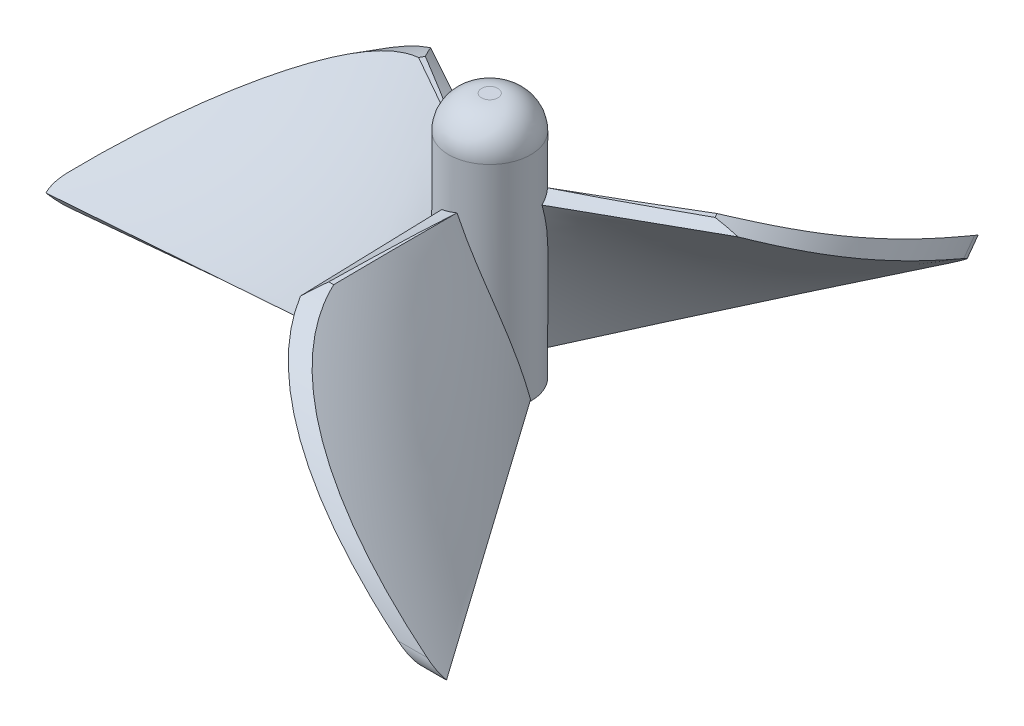
SolidWorks part; units mm, degrees
material "ABS"
ref_plane "Front Plane" through (0, 0, 0) normal (0, 0, 1) x (1, 0, 0)
ref_plane "Top Plane" through (0, 0, 0) normal (0, 1, 0) x (1, 0, 0)
ref_plane "Right Plane" through (0, 0, 0) normal (1, 0, 0) x (0, 0, -1)
sketch "Sketch1" plane through (0, 0, 0) normal (0, 1, 0) x (1, 0, 0)
  circle A0 centre (0, 0) radius 2.5
extrude "Boss-Extrude1" add sketch "Sketch1" along normal blind 15
sketch "Sketch2" plane through (0, 0, 0) normal (0, 0, 1) x (1, 0, 0)
  line L0 (-2.5, 0) -> (2.5, 0) construction
  line L1 (-0.4903, 9.9019) -> (0.4903, 10.0981)
  line L2 (-0.4903, 9.9019) -> (1.5097, -0.0981)
  line L3 (0.4903, 10.0981) -> (2.4903, 0.0981)
  line L6 (1.5097, -0.0981) -> (2.4903, 0.0981)
  point P0 (0, 10)
  point P1 (2, 0)
  dimension "D1" = 10
  dimension "D2" = 2
ref_plane "Plane1" through (0, 0, 18) normal (0, 0, 1) x (1, 0, 0)
sketch "Sketch3" plane through (0, 0, 18) normal (0, 0, 1) x (1, 0, 0)
  line L0 (0.2774, 10.416) -> (-0.2774, 9.584)
  line L2 (-0.2774, 9.584) -> (14.7226, -0.416)
  line L3 (0.2774, 10.416) -> (15.2774, 0.416)
  line L4 (15.2774, 0.416) -> (14.7226, -0.416)
  point P0 (15, 0)
  dimension "D1" = 15
loft "Loft1" add profiles "Sketch2", "Sketch3"
sketch "Sketch4" plane through (0, 0, 0) normal (1, 0, 0) x (0, 0, -1)
  line L0 (2.5, 15) -> (-2.5, 15) construction
  line L1 (-2.5, 0) -> (-16.8737, 0)
  line L2 (-18, -0.416) -> (-18, 0.416) construction
  line L3 (-2.5, 10.1415) -> (-10, 10.1415)
  line L4 (-2.5, 10.7606) -> (-2.5, 10.1415)
  line L5 (-2.5, 15) -> (-2.5, 10) construction
  line L6 (-2.5, 10.7606) -> (-20.2126, 10.7606)
  line L7 (-20.2126, 10.7606) -> (-20.2126, -1.9469)
  line L8 (-20.2126, -1.9469) -> (-2.5, -1.1117)
  line L10 (-2.5, 0) -> (0, 0)
  line L11 (0, 0) -> (0, -1.1117)
  line L12 (0, -1.1117) -> (-2.5, -1.1117)
  arc A0 (-10, 10.1415) -> (-17.859, 1.1706) centre (-6.5812, -0.7816) ccw
  arc A1 (-17.859, 1.1706) -> (-16.8737, 0) centre (-16.8737, 1) ccw
  point P0 (0, 15)
  point P1 (-10, 15)
  point P4 (-2.4571, 10.1415)
  point P5 (-10, 10.1415)
  point P17 (-18, 0)
  dimension "D2" = 1
  dimension "D1" = 10
extrude "Cut-Extrude1" cut sketch "Sketch4" along normal blind 20 and the other way blind 4
ref_axis "Axis1" through (0, 15, 0) along (0, -1, 0)
pattern_circular "CirPattern1" count 3 over 360 about axis through (0, 15, 0) along (0, -1, 0) of "Loft1", "Cut-Extrude1"
sketch "Sketch5" plane through (0, 0, 0) normal (0, -1, 0) x (1, 0, 0)
  circle A0 centre (0, 0) radius 1
extrude "Cut-Extrude2" cut sketch "Sketch5" against normal blind 8
fillet "Fillet1" radius 2 1 edges at (0, 15, 2.5)
